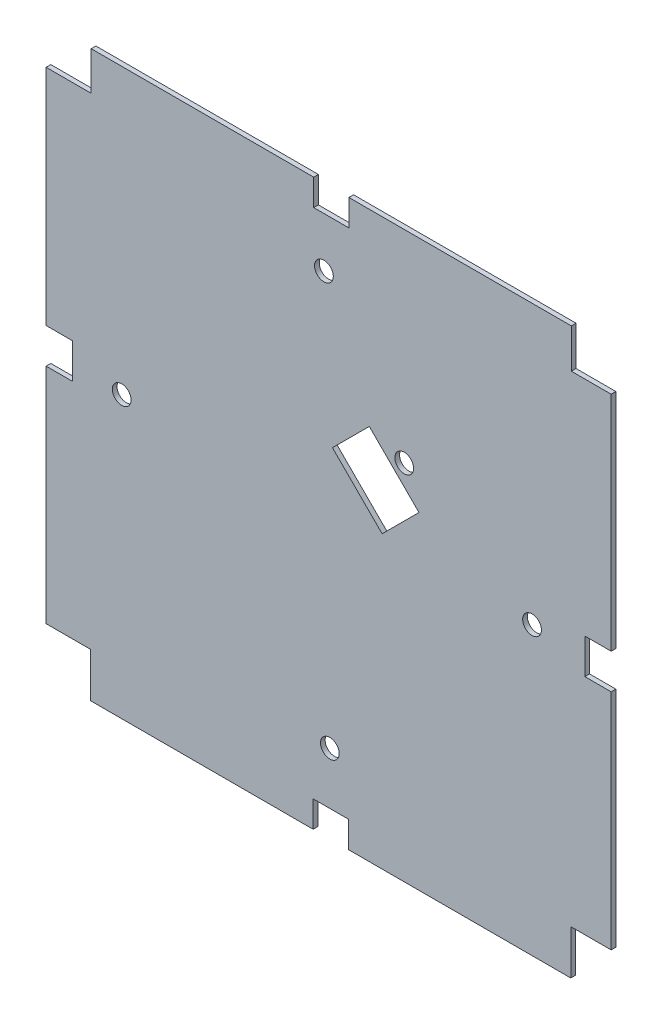
SolidWorks part; units mm, degrees
ref_plane "Front Plane" through (0, 0, 0) normal (0, 0, 1) x (1, 0, 0)
ref_plane "Top Plane" through (0, 0, 0) normal (0, 1, 0) x (1, 0, 0)
ref_plane "Right Plane" through (0, 0, 0) normal (1, 0, 0) x (0, 0, -1)
sketch "Sketch1" plane through (0, 0, 0) normal (0, 0, 1) x (1, 0, 0)
  line L1 (-67.0283, 35.647) -> (29.4717, 35.647)
  line L2 (-67.0283, 35.647) -> (-67.0283, -60.853)
  line L3 (-67.0283, -60.853) -> (29.4717, -60.853)
  line L4 (29.4717, 35.647) -> (29.4717, -60.853)
  line L5 (-67.0283, 35.647) -> (-59.3283, 35.647)
  line L6 (-67.0283, 35.647) -> (-67.0283, 29.047)
  line L7 (-67.0283, 29.047) -> (-59.3283, 29.047)
  line L8 (-59.3283, 35.647) -> (-59.3283, 29.047)
  line L21 (-67.0283, -9.153) -> (-62.5283, -9.153)
  line L22 (-67.0283, -9.153) -> (-67.0283, -15.153)
  line L23 (-67.0283, -15.153) -> (-62.5283, -15.153)
  line L24 (-62.5283, -9.153) -> (-62.5283, -15.153)
  line L25 (29.4717, 35.647) -> (22.6717, 35.647)
  line L26 (29.4717, 35.647) -> (29.4717, 28.947)
  line L27 (29.4717, 28.947) -> (22.6717, 28.947)
  line L28 (22.6717, 35.647) -> (22.6717, 28.947)
  line L29 (29.4717, -15.073) -> (24.9717, -15.073)
  line L30 (29.4717, -15.073) -> (29.4717, -9.073)
  line L31 (29.4717, -9.073) -> (24.9717, -9.073)
  line L32 (24.9717, -15.073) -> (24.9717, -9.073)
  line L33 (29.4717, -60.853) -> (22.5717, -60.853)
  line L34 (29.4717, -60.853) -> (29.4717, -53.253)
  line L35 (29.4717, -53.253) -> (22.5717, -53.253)
  line L36 (22.5717, -60.853) -> (22.5717, -53.253)
  line L37 (-67.0283, -60.853) -> (-59.4283, -60.853)
  line L38 (-67.0283, -60.853) -> (-67.0283, -53.253)
  line L39 (-67.0283, -53.253) -> (-59.4283, -53.253)
  line L40 (-59.4283, -60.853) -> (-59.4283, -53.253)
  line L42 (-21.3283, 35.647) -> (-15.3283, 35.647)
  line L43 (-21.3283, 35.647) -> (-21.3283, 31.147)
  line L44 (-21.3283, 31.147) -> (-15.3283, 31.147)
  line L45 (-15.3283, 35.647) -> (-15.3283, 31.147)
  line L47 (-21.4283, -60.853) -> (-15.4283, -60.853)
  line L48 (-21.4283, -60.853) -> (-21.4283, -56.353)
  line L49 (-21.4283, -56.353) -> (-15.4283, -56.353)
  line L50 (-15.4283, -60.853) -> (-15.4283, -56.353)
  circle A0 centre (15.9595, -11.903) radius 1.6
  circle A1 centre (-19.5872, 22.6348) radius 1.6
  circle A2 centre (-18.5783, -47.4496) radius 1.6
  circle A3 centre (-54.125, -12.9118) radius 1.6
  circle A4 centre (-5.8709, 1.097) radius 1.6
  circle A5 centre (15.9595, -11.903) radius 1.7 construction
  circle A6 centre (-54.125, -12.9118) radius 1.7 construction
  circle A7 centre (-19.5872, 22.6348) radius 1.7 construction
  circle A8 centre (-18.5783, -47.4496) radius 1.7 construction
  circle A10 centre (-5.8709, 1.097) radius 1.6 construction
  dimension "D17" = 3.2
  dimension "D19" = 3.2
  dimension "D20" = 3.2
  dimension "D21" = 3.2
  dimension "D27" = 3.2
  dimension "D16" = 0
  dimension "D22" = 0
  dimension "D23" = 0
  dimension "D1" = 96.5
  dimension "D2" = 96.5
  dimension "D3" = 4.5
  dimension "D4" = 7.7
  dimension "D5" = 6.6
  dimension "D6" = 6
  dimension "D7" = 45.7
  dimension "D8" = 7.6
  dimension "D9" = 7.6
  dimension "D10" = 6.9
  dimension "D11" = 7.6
  dimension "D12" = 6
  dimension "D13" = 4.5
  dimension "D14" = 6.7
  dimension "D15" = 6.8
  dimension "D18" = 0
  dimension "D25" = 0
  dimension "D28" = 4.5
  dimension "D29" = 6
  dimension "D30" = 45.7
  dimension "D33" = 4.5
  dimension "D34" = 6
  dimension "D35" = 45.6
extrude "Boss-Extrude1" add sketch "Sketch1" along normal blind 0.8 contours L40 L3 L36 L35 L4 L29 L32 L31 L27 L28 L1 L8 L7 L2 L21 L24 L23 L39 A4 A3 A2 A1 A0 region at (-18.7431, -12.5555, 0)
sketch "Sketch2" plane through (0, 0, 0.8) normal (0, 0, 1) x (1, 0, 0)
  line L0 (-11.8377, 3.523) -> (-3.3524, -4.9623)
  line L1 (-11.8377, 3.523) -> (-18.1309, -2.7703)
  line L2 (-3.3524, -4.9623) -> (-9.6457, -11.2556)
  line L3 (-18.1309, -2.7703) -> (-9.6457, -11.2556)
  line L4 (-16.4205, -1.0599) -> (-7.9353, -9.5452)
  line L5 (-5.0361, -6.646) -> (-13.5214, 1.8392)
  line L6 (-59.4283, -60.853) -> (-21.4283, -60.853) construction
  line L7 (-67.0283, -15.153) -> (-67.0283, -53.253) construction
  point P10 (-10.7283, -3.853)
  dimension "D1" = 45
  dimension "D2" = 8.9
  dimension "D3" = 12
  dimension "D4" = 4.1
  dimension "D5" = 2.05
  dimension "D6" = 6
  dimension "D7" = 56.3
  dimension "D8" = 57
extrude "Cut-Extrude1" cut sketch "Sketch2" against normal blind 0.8 contours L4 L1 L3 L2 | L2 L5 L1 L4 | L5 L2 L0 L1 region at (-8.4369, -1.5615, 0.8) region at (-10.7283, -3.853, 0.8) region at (-13.0331, -6.1577, 0.8)
equation "\"D5@Sketch2\"=\"D4@Sketch2\"/2"
equation "\"D6@Sketch2\"=\"D3@Sketch2\"/2"
